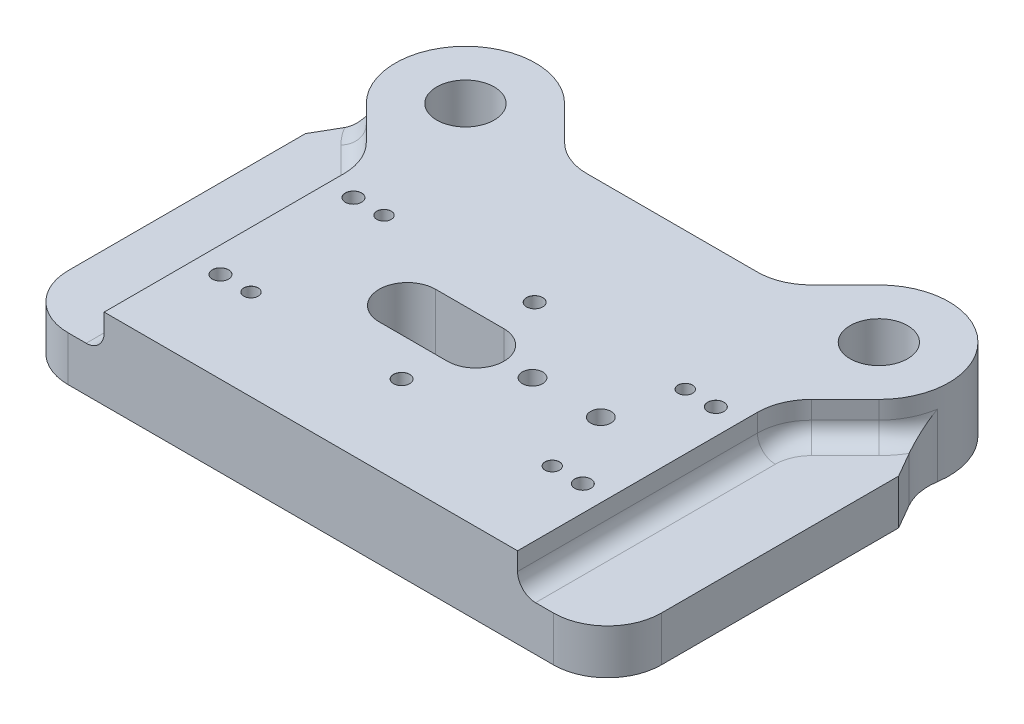
SolidWorks part; units mm, degrees
material "Plain Carbon Steel"
ref_plane "Front Plane" through (0, 0, 0) normal (0, 0, 1) x (1, 0, 0)
ref_plane "Top Plane" through (0, 0, 0) normal (0, 1, 0) x (1, 0, 0)
ref_plane "Right Plane" through (0, 0, 0) normal (1, 0, 0) x (0, 0, -1)
sketch "Sketch1" plane through (0, 0, 0) normal (0, 1, 0) x (1, 0, 0)
  line L0 (0, 120) -> (0, -120) construction
  line L1 (-165, 120) -> (165, 120) construction
  line L2 (-165, 120) -> (-165, -120) construction
  line L3 (-165, -120) -> (165, -120) construction
  line L4 (165, 120) -> (165, -120) construction
  line L5 (-165, 120) -> (165, -120) construction
  line L6 (-165, -120) -> (165, 120) construction
  line L7 (165, -120) -> (-165, -120)
  line L8 (-165, -120) -> (-165, 42)
  line L9 (-165, 42) -> (-157.2136, 55.4865)
  line L10 (-115, 42) -> (-165, 42) construction
  line L11 (-157.2136, 55.4865) -> (-151.06, 66.1448) construction
  line L12 (-87.4228, 108.5772) -> (-59.8457, 81)
  line L13 (-59.8457, 81) -> (59.8457, 81)
  line L14 (59.8457, 81) -> (87.4228, 108.5772)
  line L15 (165, 42) -> (157.2136, 55.4865)
  line L16 (165, -120) -> (165, 42)
  arc A0 (-87.4228, 108.5772) -> (-153.5446, 75.0576) centre (-115, 81) ccw
  arc A1 (87.4228, 108.5772) -> (153.5446, 75.0576) centre (115, 81) cw
  arc A2 (-157.2136, 55.4865) -> (-153.5446, 75.0576) centre (-183.1943, 70.4865) ccw
  arc A3 (-165, 94.3395) -> (-165, 46.6335) centre (-183.1943, 70.4865) ccw construction
  arc A4 (-165, 46.6335) -> (-157.2136, 55.4865) centre (-183.1943, 70.4865) ccw construction
  arc A5 (-153.5446, 75.0576) -> (-165, 94.3395) centre (-183.1943, 70.4865) ccw construction
  arc A6 (157.2136, 55.4865) -> (153.5446, 75.0576) centre (183.1943, 70.4865) cw
  arc A7 (-153.5446, 75.0576) -> (-151.06, 66.1448) centre (-115, 81) ccw construction
  arc A8 (-151.06, 66.1448) -> (-115, 42) centre (-115, 81) ccw construction
  arc A9 (-115, 42) -> (-82.2524, 59.8199) centre (-115, 81) ccw construction
  arc A10 (-82.2524, 59.8199) -> (-87.4228, 108.5772) centre (-115, 81) ccw construction
  arc A11 (153.5446, 75.0576) -> (82.2524, 59.8199) centre (115, 81) cw construction
  arc A12 (82.2524, 59.8199) -> (87.4228, 108.5772) centre (115, 81) cw construction
  point P0 (0, 0)
  dimension "D6" = 60
  dimension "D1" = 330
  dimension "D2" = 240
  dimension "D3" = 201
  dimension "D4" = 230
  dimension "D5" = 30
  dimension "D7" = 45
extrude "Boss-Extrude1" add sketch "Sketch1" along normal blind 45
fillet "Fillet1" radius 30 2 edges at (59.8457, 22.5, -81) (-59.8457, 22.5, -81)
fillet "Fillet2" radius 30 2 edges at (165, 22.5, 120) (-165, 22.5, 120)
sketch "Sketch2" plane through (0, 0, 0) normal (0, 1, 0) x (1, 0, 0)
  circle A0 centre (-115, 81) radius 16
  circle A1 centre (115, 81) radius 16
  dimension "D1" = 32
extrude "Cut-Extrude1" cut sketch "Sketch2" along normal up to next
sketch "Sketch4" plane through (0, 45, 0) normal (0, 1, 0) x (1, 0, 0)
  line L0 (0, -120) -> (0, 81) construction
  line L1 (-135, -120) -> (135, -120) construction
  line L2 (47.4193, 81) -> (-47.4193, 81) construction
  line L3 (-142.5772, 53.4228) -> (-115, 25.8457)
  line L4 (-115, -120) -> (115, -120) construction
  line L5 (-115, -120) -> (-115, 55) construction
  line L6 (-115, 55) -> (115, 55) construction
  line L7 (115, -120) -> (115, 55) construction
  line L8 (-115, 25.8457) -> (-115, -120)
  line L9 (-165, 42) -> (-165, -90) construction
  line L10 (-157.2136, 55.4865) -> (-165, 42) construction
  line L11 (-165, 42) -> (-165, -90)
  line L12 (-157.2136, 55.4865) -> (-165, 42)
  line L13 (-135, -120) -> (-115, -120)
  arc A0 (-87.4228, 108.5772) -> (-153.5446, 75.0576) centre (-115, 81) ccw construction
  circle A1 centre (-115, 81) radius 39 construction
  arc A2 (-165, -90) -> (-135, -120) centre (-135, -90) ccw construction
  arc A3 (-157.2136, 55.4865) -> (-153.5446, 75.0576) centre (-183.1943, 70.4865) ccw construction
  arc A4 (-165, -90) -> (-135, -120) centre (-135, -90) ccw
  arc A5 (-157.2136, 55.4865) -> (-153.5446, 75.0576) centre (-183.1943, 70.4865) ccw
  arc A6 (-142.5772, 53.4228) -> (-153.5446, 75.0576) centre (-115, 81) cw
  dimension "D1" = 230
  dimension "D2" = 175
  dimension "D3" = 45
extrude "Cut-Extrude2" cut sketch "Sketch4" against normal blind 20
fillet "Fillet3" radius 30 1 edges at (-115, 35, -25.8457)
mirror "Mirror1" about plane through (0, 0, 0) normal (1, 0, 0) of "Fillet3", "Cut-Extrude2"
fillet "Fillet4" radius 10 8 edges at (-149.7856, 25, -63.3659) (-133.182, 25, -44.0277) (-117.2836, 25, -24.8998) (149.7856, 25, -63.3659) (133.182, 25, -44.0277) (117.2836, 25, -24.8998) (-115, 25, 53.2904) (115, 25, 53.2904)
sketch "Sketch5" plane through (0, 45, 0) normal (0, 1, 0) x (1, 0, 0)
  line L0 (-33.8, -48.207) -> (4.2, -48.207)
  line L1 (-33.8, -16.793) -> (4.2, -16.793)
  arc A3 (-33.8, -16.793) -> (-33.8, -48.207) centre (-33.8, -32.5) ccw
  arc A4 (4.2, -48.207) -> (4.2, -16.793) centre (4.2, -32.5) ccw
extrude "Cut-Extrude3" cut sketch "Sketch5" against normal through all
sketch "Sketch6" plane through (0, 45, 0) normal (0, 1, 0) x (1, 0, 0)
  circle A0 centre (73.8, -32.5) radius 5.6699
  circle A1 centre (35.8, -32.5) radius 5.6699
extrude "Cut-Extrude4" cut sketch "Sketch6" against normal through all
sketch "Sketch7" plane through (0, 0, 0) normal (0, -1, 0) x (-1, 0, 0)
sketch "Sketch9" plane through (0, 0, 0) normal (0, -1, 0) x (-1, 0, 0)
  point P0 (100.8, 4.5)
  point P3 (100.8, -69.5)
  point P6 (-100.8, -69.5)
  point P9 (-100.8, 4.5)
  point P13 (0, -69.5)
  point P16 (0, 4.5)
hole_wizard "CBORE for M8 Hex Socket Head Cap Screw1" positions "Sketch9" profile "Sketch8" counterbore size "M8" standard "ISO" end condition through all
sketch "Sketch8" plane through (-100.8, 0, -4.5) normal (1, 0, 0) x (0, 0, -1)
  line L0 (0, 0) -> (0, 45)
  line L1 (4.5, 44.975) -> (4.525, 45)
  line L2 (7.5, 8.6) -> (4.5, 8.6)
  line L3 (4.5, 8.6) -> (4.5, 44.975)
  line L5 (7.5, 8.6) -> (7.5, 0.025)
  line L6 (7.5, 0.025) -> (7.525, 0)
  line L7 (7.525, 0) -> (0, 0)
  line L8 (-7.5, 0.025) -> (-7.525, 0) construction
  line L11 (0, -6.35) -> (0, 107.95) construction
  line L12 (4.525, 45) -> (0, 45)
  line L13 (-4.5, 44.975) -> (-4.525, 45) construction
  dimension "Thru Hole Dia." = 9
  dimension "Thru Hole Depth" = 45
  dimension "C'Bore Dia." = 15
  dimension "C'Bore Depth" = 8.6
  dimension "Near C'Sink Dia." = 15.05
  dimension "Near C'Sink Angle" = 90
  dimension "Far C'Sink Dia." = 9.05
  dimension "Far C'Sink Angle" = 90
sketch "Sketch10" plane through (0, 0, 0) normal (0, -1, 0) x (-1, 0, 0)
  point P0 (83.8, 4.5)
  point P3 (83.8, -69.5)
  point P6 (-83.8, -69.5)
  point P9 (-83.8, 4.5)
hole_wizard "Ø8.0mm Dowel Hole1" positions "Sketch10" profile "Sketch11" hole size "Ø8.0" standard "ISO" end condition through all
sketch "Sketch11" plane through (-83.8, 0, -4.5) normal (1, 0, 0) x (0, 0, -1)
  line L0 (0, 0) -> (0, 45)
  line L1 (0, 45) -> (4.025, 45)
  line L2 (4, 44.975) -> (4, 0.025)
  line L3 (4, 0.025) -> (4.025, 0)
  line L5 (4.025, 0) -> (0, 0)
  line L6 (-4, 0.025) -> (-4.025, 0) construction
  line L7 (4.025, 45) -> (4, 44.975)
  line L8 (-4.025, 45) -> (-4, 44.975) construction
  line L11 (0, -6.35) -> (0, 107.95) construction
  dimension "Thru Hole Dia." = 8
  dimension "Thru Hole Depth" = 45
  dimension "Near C'Sink Dia." = 8.05
  dimension "Near C'Sink Angle" = 90
  dimension "Far C'Sink Dia." = 8.05
  dimension "Far C'Sink Angle" = 90
